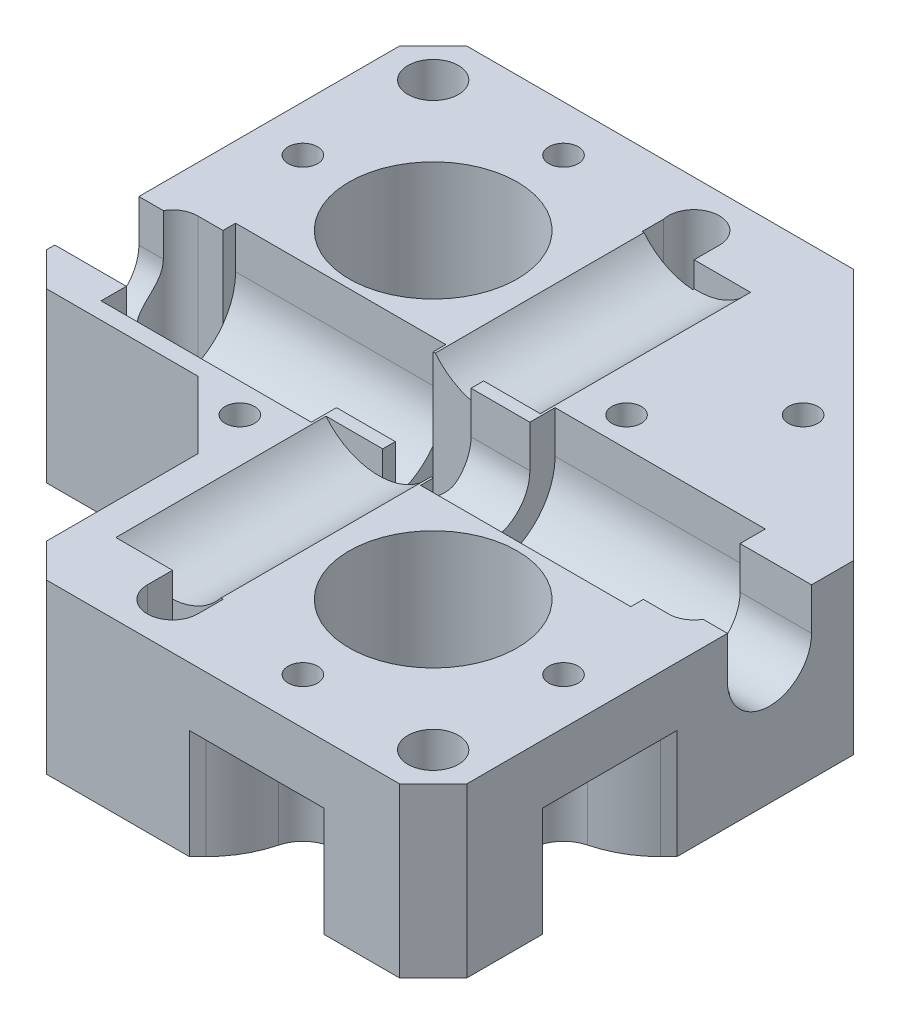
SolidWorks part; units mm, degrees
ref_plane "Front Plane" through (0, 0, 0) normal (0, 0, 1) x (1, 0, 0)
ref_plane "Top Plane" through (0, 0, 0) normal (0, 1, 0) x (1, 0, 0)
ref_plane "Right Plane" through (0, 0, 0) normal (1, 0, 0) x (0, 0, -1)
sketch "Sketch1" plane through (0, 0, 0) normal (0, 1, 0) x (1, 0, 0)
  line L1 (-40, -40) -> (40, -40)
  line L2 (-40, -40) -> (-40, 40)
  line L3 (-40, 40) -> (40, 40)
  line L4 (40, -40) -> (40, 40)
  line L5 (-40, -40) -> (40, 40) construction
  line L6 (-40, 40) -> (40, -40) construction
  point P0 (0, 0)
  dimension "D1" = 80
  dimension "D2" = 80
extrude "Boss-Extrude1" add sketch "Sketch1" against normal blind 20
sketch "Sketch2" plane through (0, 0, 0) normal (0, 1, 0) x (1, 0, 0)
  circle A0 centre (-11.5, -11.5) radius 1.75
  circle A1 centre (11.5, 11.5) radius 1.75
  circle A2 centre (22, 22) radius 1.75
  circle A3 centre (19, -34.5) radius 1.75
  circle A4 centre (34.5, -19) radius 1.75
  circle A5 centre (-34.5, 19) radius 1.75
  circle A6 centre (-19, 34.5) radius 1.75
  dimension "D1" = 3.5
  dimension "D2" = 3.5
  dimension "D3" = 3.5
  dimension "D4" = 3.5
  dimension "D5" = 3.5
  dimension "D6" = 3.5
  dimension "D7" = 3.5
  dimension "D8" = 11.5
  dimension "D9" = 11.5
  dimension "D10" = 11.5
  dimension "D11" = 11.5
  dimension "D12" = 22
  dimension "D13" = 22
  dimension "D14" = 34.5
  dimension "D15" = 34.5
  dimension "D16" = 19
  dimension "D17" = 19
  dimension "D18" = 34.5
  dimension "D19" = 19
  dimension "D20" = 19
  dimension "D21" = 34.5
extrude "Cut-Extrude1" cut sketch "Sketch2" against normal through all both and the other way through all
sketch "Sketch3" plane through (0, 0, 0) normal (0, 1, 0) x (1, 0, 0)
  line L1 (31.5, -8) -> (6.5, -8)
  line L2 (31.5, -8) -> (31.5, 8)
  line L3 (31.5, 8) -> (6.5, 8)
  line L4 (6.5, -8) -> (6.5, 8)
  line L5 (31.5, -8) -> (6.5, 8) construction
  line L6 (31.5, 8) -> (6.5, -8) construction
  line L7 (-6.5, -8) -> (-31.5, -8)
  line L8 (-6.5, -8) -> (-6.5, 8)
  line L9 (-6.5, 8) -> (-31.5, 8)
  line L10 (-31.5, -8) -> (-31.5, 8)
  line L11 (-6.5, -8) -> (-31.5, 8) construction
  line L12 (-6.5, 8) -> (-31.5, -8) construction
  point P0 (19, 0)
  point P5 (-19, 0)
  dimension "D1" = 16
  dimension "D2" = 0
  dimension "D3" = 25
  dimension "D4" = 19
  dimension "D5" = 25
  dimension "D6" = 16
  dimension "D7" = 0
  dimension "D8" = 19
extrude "Cut-Extrude2" cut sketch "Sketch3" against normal blind 13
fillet "Fillet1" radius 8 4 edges at (19, -13, 8) (19, -13, -8) (-19, -13, 8) (-19, -13, -8)
sketch "Sketch4" plane through (0, 0, 0) normal (0, 1, 0) x (1, 0, 0)
  line L1 (-8, -31.5) -> (8, -31.5)
  line L2 (-8, -31.5) -> (-8, -6.5)
  line L3 (-8, -6.5) -> (8, -6.5)
  line L4 (8, -31.5) -> (8, -6.5)
  line L5 (-8, -31.5) -> (8, -6.5) construction
  line L6 (-8, -6.5) -> (8, -31.5) construction
  line L7 (-8, 6.5) -> (8, 6.5)
  line L8 (-8, 6.5) -> (-8, 31.5)
  line L9 (-8, 31.5) -> (8, 31.5)
  line L10 (8, 6.5) -> (8, 31.5)
  point P0 (0, -19)
  dimension "D1" = 16
  dimension "D2" = 0
  dimension "D3" = 25
  dimension "D4" = 19
  dimension "D5" = 25
  dimension "D6" = 6.5
extrude "Cut-Extrude3" cut sketch "Sketch4" against normal blind 3
sketch3d "3DSketch1" [suppressed]
  line L1 (-8, -3, 8) -> (8, -3, 8)
  line L2 (-8, -3, 8) -> (-8, 0, 8)
  line L3 (-8, 0, 8) -> (8, 0, 8)
  line L4 (8, -3, 8) -> (8, 0, 8)
  circle A0 centre (0, 5, 8) radius 8
  point P2 (0, 5, 16)
  point P3 (0, 0, 8)
  point P5 (0, 0, 8)
  dimension "D4" = 16
  dimension "D1" = 8
  dimension "D2" = 0
  dimension "D3" = 5
sketch "Sketch5" plane through (0, 0, 31.5) normal (0, 0, -1) x (-1, 0, 0)
  line L0 (8, -3) -> (-8, -3) construction
  line L5 (8, 0) -> (-8, 0)
  line L6 (-8, 0) -> (-8, -3)
  line L7 (-8, -3) -> (8, -3)
  line L8 (8, -3) -> (8, 0)
  line L9 (8, 0) -> (-8, 0)
  line L10 (-8, 0) -> (-8, -3)
  line L11 (-8, -3) -> (8, -3)
  line L12 (8, -3) -> (8, 0)
  circle A0 centre (0, 5) radius 8
  line M6 (8, 0) -> (-8, 0)
  line M7 (-8, 0) -> (-8, -3)
  line M8 (-8, -3) -> (8, -3)
  line M9 (8, -3) -> (8, 0)
  dimension "D2" = 16
  dimension "D1" = 8
  dimension "D3" = 0
extrude "Boss-Extrude2" add sketch "Sketch5" along normal blind 23.5 contours A0 M6 M7 M8 | A0 L11 M9 M6 region at (-5.8898, -1.8317, 31.5) region at (5.8898, -1.8317, 31.5)
mirror "Mirror1" about plane through (0, 0, 0) normal (0, 0, 1) of "Boss-Extrude2"
sketch "Sketch6" plane through (0, 0, 0) normal (1, 0, 0) x (0, 0, -1)
  line L1 (5, -5) -> (-5, -5)
  line L2 (5, -5) -> (5, 0)
  line L3 (5, 0) -> (-5, 0)
  line L4 (-5, -5) -> (-5, 0)
  circle A0 centre (0, -5) radius 5
  dimension "D2" = 10
  dimension "D1" = 5
extrude "Cut-Extrude4" cut sketch "Sketch6" against normal through all both and the other way through all contours L1 A0 | A0 L3 L4 | A0 L2 L3 | L1 A0 region at (0, -7.1221, 0) region at (0, -1.1168, -3.8832) region at (0, -2.8779, 0) region at (0, -1.1168, 3.8832)
sketch "Sketch7" plane through (0, 0, 0) normal (0, 1, 0) x (1, 0, 0)
  circle A0 centre (19, -19) radius 10
  circle A1 centre (-19, 19) radius 10
  dimension "D5" = 20
  dimension "D6" = 20
  dimension "D1" = 19
  dimension "D2" = 19
  dimension "D3" = 19
  dimension "D4" = 19
extrude "Cut-Extrude5" cut sketch "Sketch7" against normal through all both and the other way through all
sketch "Sketch8" plane through (0, 0, -6.5) normal (0, 0, -1) x (-1, 0, 0)
  line L4 (6.5, 0) -> (-6.5, 0)
  line L5 (-6.5, 0) -> (-6.5, -3)
  line L6 (-6.5, -3) -> (6.5, -3)
  line L7 (6.5, -3) -> (6.5, 0)
  line L8 (6.5, 0) -> (-6.5, 0)
  line L9 (-6.5, 0) -> (-6.5, -3)
  line L10 (-6.5, -3) -> (6.5, -3)
  line L11 (6.5, -3) -> (6.5, 0)
  arc A0 (0, -3) -> (6.245, 0) centre (0, 5) ccw construction
  arc A1 (-6.245, 0) -> (0, -3) centre (0, 5) ccw construction
  arc A2 (0, -3) -> (6.245, 0) centre (0, 5) ccw
  arc A3 (-6.245, 0) -> (0, -3) centre (0, 5) ccw
  line M5 (6.5, 0) -> (-6.5, 0)
  line M6 (-6.5, 0) -> (-6.5, -3)
  line M7 (-6.5, -3) -> (6.5, -3)
  line M8 (6.5, -3) -> (6.5, 0)
  dimension "D1" = 0
extrude "Boss-Extrude3" add sketch "Sketch8" along normal blind 1.5 contours A3 M5 M6 M7 | A2 L10 M8 M5 region at (-4.9409, -2.063, -6.5) region at (4.9409, -2.063, -6.5)
mirror "Mirror2" about plane through (0, 0, 0) normal (0, 0, 1) of "Boss-Extrude3"
sketch "Sketch9" plane through (0, 0, 0) normal (0, 1, 0) x (1, 0, 0)
  line L0 (-10, -18) -> (-18, -10)
  line L1 (-40, -40) -> (-10, -40)
  line L2 (-40, -40) -> (-40, -10)
  line L3 (-40, -10) -> (-10, -10)
  line L4 (-10, -40) -> (-10, -10)
  line L5 (-10, -10) -> (-18, -10)
  line L6 (-10, -10) -> (-10, -18)
  line L7 (-10, -18) -> (-18, -18)
  line L8 (-18, -10) -> (-18, -18)
  dimension "D1" = 30
  dimension "D2" = 30
  dimension "D3" = 8
  dimension "D4" = 8
extrude "Cut-Extrude6" cut sketch "Sketch9" against normal through all both and the other way through all contours L0 L8 L7 | L8 L3 L2 L1 L4 L7 region at (-15.3333, 0, 15.3333) region at (-25.8421, 0, 25.8421)
chamfer "Chamfer1" distance 4 angle 45 4 edges at (40, -10, 40) (-40, -10, -40) (-40, -10, 10) (-10, -10, 40)
chamfer "Chamfer2" distance 30 angle 45 1 edges at (40, -10, -40)
sketch "Sketch10" plane through (0, 0, 0) normal (0, 1, 0) x (1, 0, 0)
  circle A0 centre (3.5, -3.5) radius 1.75
  circle A1 centre (-3.5, 3.5) radius 1.75
  circle A2 centre (34.5, -3.5) radius 1.75
  circle A3 centre (3.5, -34.5) radius 1.75
  circle A4 centre (34.5, -34.5) radius 1.75
  circle A5 centre (-3.5, 34.5) radius 1.75
  circle A6 centre (-34.5, 3.5) radius 1.75
  circle A7 centre (-34.5, 34.5) radius 1.75
  dimension "D5" = 3.5
  dimension "D6" = 3.5
  dimension "D8" = 3.5
  dimension "D10" = 3.5
  dimension "D11" = 3.5
  dimension "D12" = 3.5
  dimension "D13" = 3.5
  dimension "D16" = 3.5
  dimension "D1" = 3.5
  dimension "D2" = 3.5
  dimension "D3" = 3.5
  dimension "D4" = 3.5
  dimension "D7" = 31
  dimension "D9" = 31
  dimension "D14" = 31
  dimension "D15" = 31
extrude "Cut-Extrude7" cut sketch "Sketch10" against normal through all both and the other way through all
sketch "Sketch11" plane through (0, 0, 0) normal (0, 1, 0) x (1, 0, 0)
  line L0 (-6.5, 5) -> (-6.5, 8) construction
  line L1 (-0.5, 3.5) -> (-6.5, 3.5)
  line L2 (-0.5, 3.5) -> (-0.5, 6.5)
  line L3 (-0.5, 6.5) -> (-6.5, 6.5)
  line L4 (-6.5, 3.5) -> (-6.5, 6.5)
  line L5 (6.5, -5) -> (6.5, -8) construction
  line L6 (0.5, -3.5) -> (6.5, -3.5)
  line L7 (0.5, -3.5) -> (0.5, -6.5)
  line L8 (0.5, -6.5) -> (6.5, -6.5)
  line L9 (6.5, -3.5) -> (6.5, -6.5)
  line L10 (31.5, -8) -> (31.5, -5) construction
  line L11 (34.5, -0.5) -> (31.5, -0.5)
  line L12 (34.5, -0.5) -> (34.5, -6.5)
  line L13 (34.5, -6.5) -> (31.5, -6.5)
  line L14 (31.5, -0.5) -> (31.5, -6.5)
  line L15 (-6.245, -31.5) -> (6.245, -31.5) construction
  line L16 (-34.5, 6.5) -> (-31.5, 6.5)
  line L17 (-34.5, 6.5) -> (-34.5, 0.5)
  line L18 (-34.5, 0.5) -> (-31.5, 0.5)
  line L19 (-31.5, 6.5) -> (-31.5, 0.5)
  line L20 (3.5, -0.5) -> (6.5, -0.5)
  line L21 (3.5, -0.5) -> (3.5, -6.5)
  line L22 (3.5, -6.5) -> (6.5, -6.5)
  line L23 (6.5, -0.5) -> (6.5, -6.5)
  line L24 (-3.5, 0.5) -> (-6.5, 0.5)
  line L25 (-3.5, 0.5) -> (-3.5, 6.5)
  line L26 (-3.5, 6.5) -> (-6.5, 6.5)
  line L27 (-6.5, 0.5) -> (-6.5, 6.5)
  line L32 (0.5, -31.5) -> (6.5, -31.5)
  line L33 (0.5, -31.5) -> (0.5, -34.5)
  line L34 (0.5, -34.5) -> (6.5, -34.5)
  line L35 (6.5, -31.5) -> (6.5, -34.5)
  line L37 (-0.4632, 34.5) -> (-6.4632, 34.5)
  line L38 (-0.4632, 34.5) -> (-0.4632, 31.3284)
  line L39 (-0.4632, 31.3284) -> (-6.4632, 31.3284)
  line L40 (-6.4632, 34.5) -> (-6.4632, 31.3284)
  circle A0 centre (-34.5, 3.5) radius 1.75 construction
  circle A1 centre (34.5, -3.5) radius 1.75 construction
  circle A2 centre (-3.5, 3.5) radius 1.75 construction
  circle A3 centre (3.5, -3.5) radius 1.75 construction
  circle A4 centre (-34.5, 3.5) radius 1.75
  circle A5 centre (34.5, -3.5) radius 1.75
  circle A6 centre (-3.5, 3.5) radius 1.75
  circle A7 centre (3.5, -3.5) radius 1.75
  circle A8 centre (-3.5, 3.5) radius 3
  circle A9 centre (3.5, -3.5) radius 3
  circle A10 centre (34.5, -3.5) radius 3
  circle A11 centre (-34.5, 3.5) radius 3
  circle A12 centre (-3.5, 34.5) radius 1.75 construction
  circle A13 centre (3.5, -34.5) radius 1.75 construction
  circle A14 centre (-3.5, 34.5) radius 1.75
  circle A15 centre (3.5, -34.5) radius 1.75
  circle A16 centre (3.5, -34.5) radius 3
  circle A17 centre (-3.5, 34.5) radius 3.0368
  dimension "D1" = 6
  dimension "D2" = 6
  dimension "D3" = 6
  dimension "D4" = 6
extrude "Cut-Extrude11" cut sketch "Sketch11" against normal blind 17 contours A17 | L40 L39 L38 L37 | L4 L1 L2 L3 | L26 L25 L24 L27 | A8 | A9 | L9 L6 L7 L8 | L22 L21 L20 L23 | L11 L14 L13 L12 | A10 | A11 | L16 L19 L18 L17 | A16 | L35 L34 L33 L32
sketch "Sketch12" plane through (0, 0, 0) normal (0, 1, 0) x (1, 0, 0)
  circle A0 centre (-34.5, 34.5) radius 1.75 construction
  circle A1 centre (34.5, -34.5) radius 1.75 construction
  circle A2 centre (-34.5, 34.5) radius 1.75
  circle A3 centre (34.5, -34.5) radius 1.75
  circle A4 centre (34.5, -34.5) radius 3
  circle A5 centre (-34.5, 34.5) radius 3
  dimension "D1" = 6
  dimension "D2" = 6
extrude "Cut-Extrude12" cut sketch "Sketch12" against normal blind 8
sketch "Sketch13" plane through (0, -20, 0) normal (0, -1, 0) x (1, 0, 0)
  circle A0 centre (-19, -19) radius 10 construction
  circle A1 centre (19, 19) radius 10 construction
  circle A2 centre (-19, -19) radius 10
  circle A3 centre (19, 19) radius 10
  circle A4 centre (19, 19) radius 11
  circle A5 centre (-19, -19) radius 11
  dimension "D1" = 22
  dimension "D2" = 22
extrude "Cut-Extrude13" cut sketch "Sketch13" against normal blind 3
sketch "Sketch14" plane through (0, -20, 0) normal (0, -1, 0) x (1, 0, 0)
  line L1 (-34.5, -15.8246) -> (-37.25, -17.4123)
  line L2 (-37.25, -17.4123) -> (-37.25, -20.5877)
  line L3 (-37.25, -20.5877) -> (-34.5, -22.1754)
  line L4 (-34.5, -22.1754) -> (-31.75, -20.5877)
  line L5 (-31.75, -20.5877) -> (-31.75, -17.4123)
  line L6 (-31.75, -17.4123) -> (-34.5, -15.8246)
  line L7 (-15.8246, -34.5) -> (-17.4123, -31.75)
  line L8 (-17.4123, -31.75) -> (-20.5877, -31.75)
  line L9 (-20.5877, -31.75) -> (-22.1754, -34.5)
  line L10 (-22.1754, -34.5) -> (-20.5877, -37.25)
  line L11 (-20.5877, -37.25) -> (-17.4123, -37.25)
  line L12 (-17.4123, -37.25) -> (-15.8246, -34.5)
  line L13 (34.5, 22.1754) -> (31.75, 20.5877)
  line L14 (31.75, 20.5877) -> (31.75, 17.4123)
  line L15 (31.75, 17.4123) -> (34.5, 15.8246)
  line L16 (34.5, 15.8246) -> (37.25, 17.4123)
  line L17 (37.25, 17.4123) -> (37.25, 20.5877)
  line L18 (37.25, 20.5877) -> (34.5, 22.1754)
  line L19 (22.1754, 34.5) -> (20.5877, 37.25)
  line L20 (20.5877, 37.25) -> (17.4123, 37.25)
  line L21 (17.4123, 37.25) -> (15.8246, 34.5)
  line L22 (15.8246, 34.5) -> (17.4123, 31.75)
  line L23 (17.4123, 31.75) -> (20.5877, 31.75)
  line L24 (20.5877, 31.75) -> (22.1754, 34.5)
  line L25 (-8.3246, 11.5) -> (-9.9123, 14.25)
  line L26 (-9.9123, 14.25) -> (-13.0877, 14.25)
  line L27 (-13.0877, 14.25) -> (-14.6754, 11.5)
  line L28 (-14.6754, 11.5) -> (-13.0877, 8.75)
  line L29 (-13.0877, 8.75) -> (-9.9123, 8.75)
  line L30 (-9.9123, 8.75) -> (-8.3246, 11.5)
  line L31 (8.3246, -11.5) -> (9.9123, -14.25)
  line L32 (9.9123, -14.25) -> (13.0877, -14.25)
  line L33 (13.0877, -14.25) -> (14.6754, -11.5)
  line L34 (14.6754, -11.5) -> (13.0877, -8.75)
  line L35 (13.0877, -8.75) -> (9.9123, -8.75)
  line L36 (9.9123, -8.75) -> (8.3246, -11.5)
  line L37 (22, -18.8246) -> (19.25, -20.4123)
  line L38 (19.25, -20.4123) -> (19.25, -23.5877)
  line L39 (19.25, -23.5877) -> (22, -25.1754)
  line L40 (22, -25.1754) -> (24.75, -23.5877)
  line L41 (24.75, -23.5877) -> (24.75, -20.4123)
  line L42 (24.75, -20.4123) -> (22, -18.8246)
  circle A0 centre (19, 34.5) radius 1.75 construction
  circle A1 centre (34.5, 19) radius 1.75 construction
  circle A2 centre (-34.5, -19) radius 1.75 construction
  circle A3 centre (22, -22) radius 1.75 construction
  circle A4 centre (11.5, -11.5) radius 1.75 construction
  circle A5 centre (-19, -34.5) radius 1.75 construction
  circle A6 centre (-11.5, 11.5) radius 1.75 construction
  circle A7 centre (19, 34.5) radius 1.75
  circle A8 centre (34.5, 19) radius 1.75
  circle A9 centre (-34.5, -19) radius 1.75
  circle A10 centre (22, -22) radius 1.75
  circle A11 centre (11.5, -11.5) radius 1.75
  circle A12 centre (-19, -34.5) radius 1.75
  circle A13 centre (-11.5, 11.5) radius 1.75
  circle A14 centre (-34.5, -19) radius 2.75 construction
  circle A15 centre (-19, -34.5) radius 2.75 construction
  circle A16 centre (34.5, 19) radius 2.75 construction
  circle A17 centre (19, 34.5) radius 2.75 construction
  circle A18 centre (-11.5, 11.5) radius 2.75 construction
  circle A19 centre (11.5, -11.5) radius 2.75 construction
  circle A20 centre (22, -22) radius 2.75 construction
  point P21 (37.25, 19)
  point P50 (-37.25, -19)
  point P51 (-19, -37.25)
  point P52 (11.5, -8.75)
  dimension "D1" = 5.5
  dimension "D2" = 5.5
  dimension "D3" = 5.5
  dimension "D4" = 5.5
  dimension "D5" = 5.5
  dimension "D6" = 5.5
  dimension "D7" = 5.5
extrude "Cut-Extrude14" cut sketch "Sketch14" against normal blind 16
sketch "Sketch15" plane through (0, -20, 0) normal (0, -1, 0) x (1, 0, 0)
  line L0 (10, -40) -> (-36, -40) construction
  line L1 (-23, -34.5) -> (-15, -34.5)
  line L2 (-23, -34.5) -> (-23, -40)
  line L3 (-23, -40) -> (-15, -40)
  line L4 (-15, -34.5) -> (-15, -40)
  line L5 (-40, -36) -> (-40, 6) construction
  line L6 (-34.5, -23) -> (-40, -23)
  line L7 (-34.5, -23) -> (-34.5, -15)
  line L8 (-34.5, -15) -> (-40, -15)
  line L9 (-40, -23) -> (-40, -15)
  line L10 (-6, 40) -> (36, 40) construction
  line L11 (15, 34.5) -> (23, 34.5)
  line L12 (15, 34.5) -> (15, 40)
  line L13 (15, 40) -> (23, 40)
  line L14 (23, 34.5) -> (23, 40)
  line L15 (40, 36) -> (40, -10) construction
  line L16 (34.5, 15) -> (40, 15)
  line L17 (34.5, 15) -> (34.5, 23)
  line L18 (34.5, 23) -> (40, 23)
  line L19 (40, 15) -> (40, 23)
  line L20 (-13.0877, 8.75) -> (-18, 10)
  line L21 (-18, 10) -> (-10, 18)
  line L22 (-10, 18) -> (-8.3246, 11.5)
  line L23 (-8.3246, 11.5) -> (-13.0877, 8.75)
  line L24 (13.0877, -8.75) -> (40, -10)
  line L25 (10, -40) -> (9.9123, -14.25)
  line L26 (9.9123, -14.25) -> (13.0877, -8.75)
  line L27 (10, -40) -> (40, -10)
  circle A0 centre (-11.5, 11.5) radius 1.75 construction
  circle A1 centre (-34.5, -19) radius 1.75 construction
  circle A2 centre (-19, -34.5) radius 1.75 construction
  circle A3 centre (22, -22) radius 1.75 construction
  circle A4 centre (11.5, -11.5) radius 1.75 construction
  circle A5 centre (34.5, 19) radius 1.75 construction
  circle A6 centre (19, 34.5) radius 1.75 construction
  circle A7 centre (-11.5, 11.5) radius 1.75
  circle A8 centre (-34.5, -19) radius 1.75
  circle A9 centre (-19, -34.5) radius 1.75
  circle A10 centre (22, -22) radius 1.75
  circle A11 centre (11.5, -11.5) radius 1.75
  circle A12 centre (34.5, 19) radius 1.75
  circle A13 centre (19, 34.5) radius 1.75
  circle A14 centre (-34.5, -19) radius 4
  circle A15 centre (-19, -34.5) radius 4
  circle A16 centre (34.5, 19) radius 4
  circle A17 centre (19, 34.5) radius 4
  dimension "D1" = 8
  dimension "D2" = 8
  dimension "D3" = 8
  dimension "D4" = 8
extrude "Cut-Extrude15" cut sketch "Sketch15" against normal blind 13 contours A11 L26 L25 L27 L24 A10 | L2 L3 L4 L1 | A15 | A14 | L8 L9 L6 L7 | L21 L22 L23 L20 | A16 | L18 L19 L16 L17 | A17 | L14 L13 L12 L11 region at (20.1853, -20, -19.7439)
chamfer "Chamfer3" distance 4 angle 45 8 edges at (40, -13.5, 23) (40, -13.5, 15) (15, -13.5, 40) (23, -13.5, 40) (-15, -13.5, -40) (-23, -13.5, -40) (-40, -13.5, -15) (-40, -13.5, -23)
fillet "Fillet2" radius 12 8 edges at (15, -13.5, 36) (23, -13.5, 36) (36, -13.5, 23) (36, -13.5, 15) (-23, -13.5, -36) (-15, -13.5, -36) (-36, -13.5, -23) (-36, -13.5, -15)
